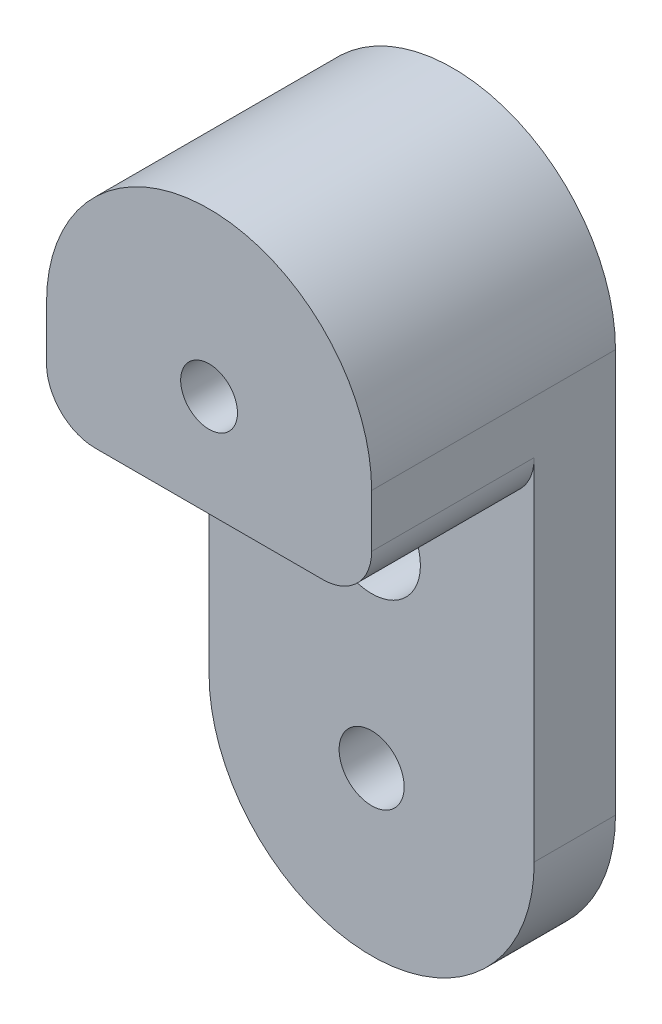
SolidWorks part; units mm, degrees
ref_plane "Front Plane" through (0, 0, 0) normal (0, 0, 1) x (1, 0, 0)
ref_plane "Top Plane" through (0, 0, 0) normal (0, 1, 0) x (1, 0, 0)
ref_plane "Right Plane" through (0, 0, 0) normal (1, 0, 0) x (0, 0, -1)
sketch "Sketch1" plane through (0, 0, 0) normal (0, 0, 1) x (1, 0, 0)
  line L0 (0, 0) -> (0, -24.8) construction
  line L1 (10, 0) -> (10, -24.8)
  line L2 (-10, 0) -> (-10, -24.8)
  line L3 (-10, -6.25) -> (10, -6.25)
  circle A0 centre (0, 0) radius 1.7462
  circle A1 centre (0, -12.5) radius 3
  circle A2 centre (0, -24.8) radius 2
  arc A3 (10, 0) -> (-10, 0) centre (0, 0) ccw
  arc A4 (-10, -24.8) -> (10, -24.8) centre (0, -24.8) ccw
  point P7 (0, -12.4)
  point P14 (0, -12.65)
  point P15 (-1.9132, -12.8584)
  dimension "D1" = 4
  dimension "D2" = 6
  dimension "D3" = 3.4925
  dimension "D4" = 12.5
  dimension "D5" = 7.3
  dimension "D6" = 20
  dimension "D7" = 12.5
  dimension "D8" = 6.25
extrude "Boss-Extrude1" add sketch "Sketch1" along normal blind 5 contours L2 A4 L1 L3 A1 A2 region at (0, -19.8197, 0)
extrude "Boss-Extrude2" add sketch "Sketch1<3>" along normal blind 15 contours A0 L3 L1 A3 L2 region at (9.7423, -3.125, 0)
sketch "Sketch1<3>" plane through (0, 0, 0) normal (0, 0, 1) x (1, 0, 0) same geometry as "Sketch1"
fillet "Fillet1" radius 3 2 edges at (10, -6.25, 10) (-10, -6.25, 10)
equation "\"D8@Sketch1\"=\"D7@Sketch1\"/2"
equation "\"D3@Sketch1\"=0.125*25.4*1.1"
